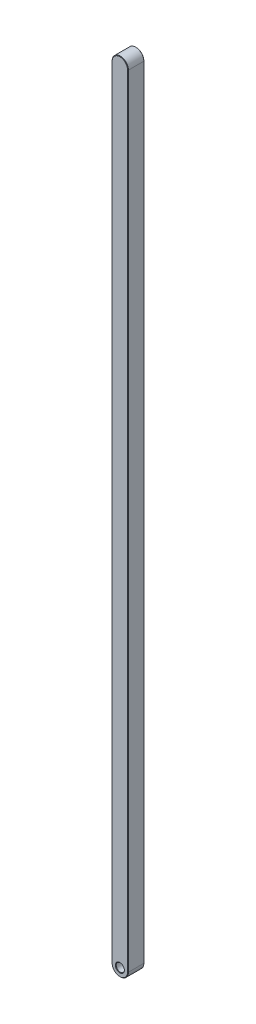
SolidWorks part; units mm, degrees
material "6061-T6 (SS)"
ref_plane "Front Plane" through (0, 0, 0) normal (0, 0, 1) x (1, 0, 0)
ref_plane "Top Plane" through (0, 0, 0) normal (0, 1, 0) x (1, 0, 0)
ref_plane "Right Plane" through (0, 0, 0) normal (1, 0, 0) x (0, 0, -1)
ref_axis "X Axis" through (88.99, 0, 0) along (-1, 0, 0)
ref_axis "Y Axis" through (0, 55, 0) along (0, -1, 0)
ref_axis "Z Axis" through (0, 0, -88.99) along (0, 0, 1)
sketch "Sketch1" plane through (0, 0, 0) normal (0, 0, 1) x (1, 0, 0)
  line L0 (0, 0) -> (0, 457.2) construction
  line L1 (-4.7625, 0) -> (-4.7625, 457.2)
  line L2 (4.7625, 0) -> (4.7625, 457.2)
  arc A0 (-4.7625, 0) -> (4.7625, 0) centre (0, 0) ccw
  arc A1 (4.7625, 457.2) -> (-4.7625, 457.2) centre (0, 457.2) ccw
  circle A2 centre (0, 0) radius 2.3813
  point P3 (0, 228.6)
  dimension "D3" = 4.7625
  dimension "D1" = 9.525
  dimension "D2" = 457.2
extrude "Boss-Extrude1" add sketch "Sketch1" along normal mid plane 9.525
chamfer "Chamfer1" distance 0.254 angle 45 10 edges at (2.3813, 0, -4.7625) (4.7625, 228.6, -4.7625) (0, 461.9625, -4.7625) (-4.7625, 228.6, -4.7625) (0, -4.7625, -4.7625) (2.3813, 0, 4.7625) (-4.7625, 228.6, 4.7625) (0, 461.9625, 4.7625) (4.7625, 228.6, 4.7625) (0, -4.7625, 4.7625)
